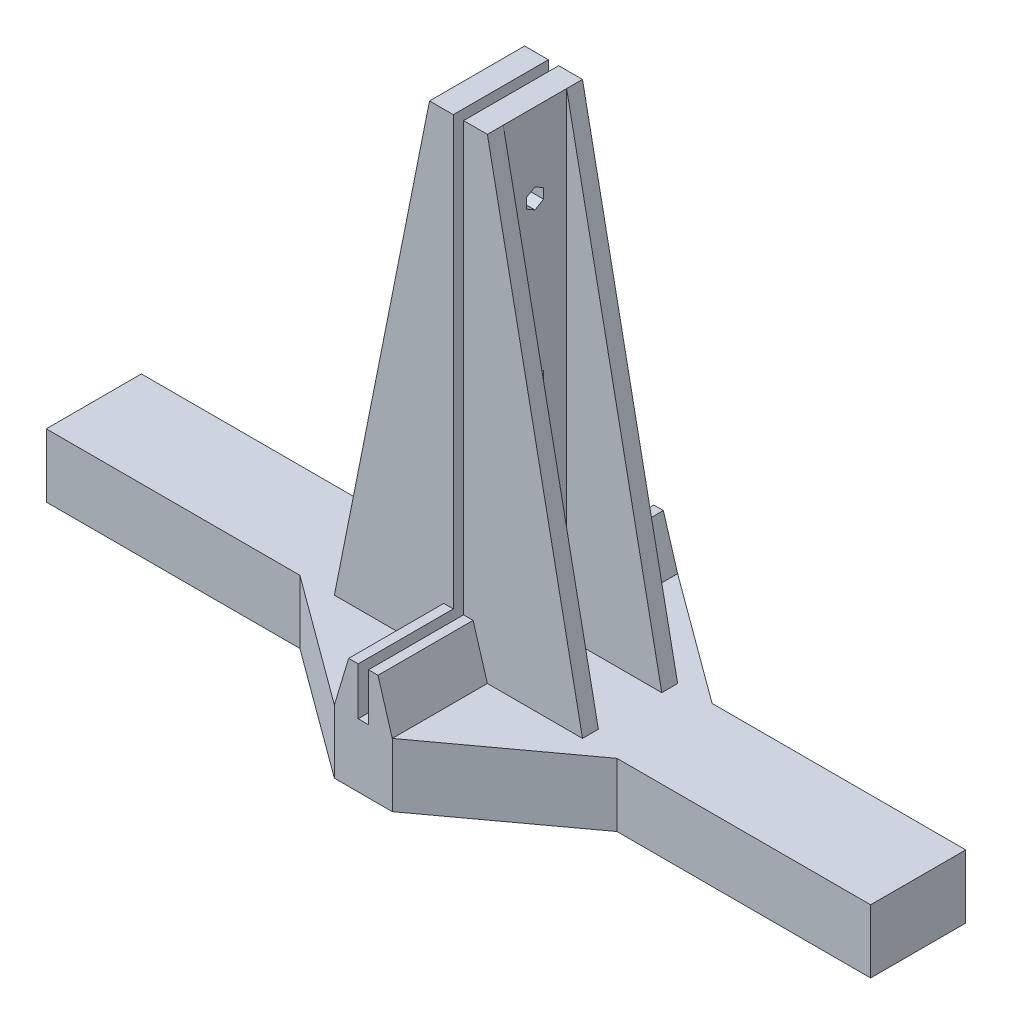
SolidWorks part; units mm, degrees
ref_plane "Front Plane" through (0, 0, 0) normal (0, 0, 1) x (1, 0, 0)
ref_plane "Top Plane" through (0, 0, 0) normal (0, 1, 0) x (1, 0, 0)
ref_plane "Right Plane" through (0, 0, 0) normal (1, 0, 0) x (0, 0, -1)
sketch "Sketch1" plane through (0, 0, 0) normal (0, 0, 1) x (1, 0, 0)
  line L0 (0, 0) -> (130, 0)
  line L1 (55, 0) -> (-55, 0) construction
  line L2 (130, 0) -> (130, 20)
  line L3 (130, 20) -> (9.125, 20)
  line L4 (9.125, 20) -> (9.125, 170)
  line L5 (9.125, 170) -> (1.625, 170)
  line L6 (1.625, 170) -> (1.625, 20)
  line L7 (1.625, 20) -> (-1.625, 20)
  line L8 (-1.625, 20) -> (-1.625, 170)
  line L9 (-1.625, 170) -> (-9.125, 170)
  line L10 (-9.125, 170) -> (-9.125, 20)
  line L11 (-9.125, 20) -> (-130, 20)
  line L12 (-130, 20) -> (-130, 0)
  line L13 (-130, 0) -> (0, 0)
  point P15 (0, 20)
  dimension "D1" = 130
  dimension "D2" = 20
  dimension "D4" = 150
  dimension "D5" = 7.5
  dimension "D6" = 3.25
  dimension "D7" = 260
  dimension "D8" = 7.5
extrude "Boss-Extrude3" add sketch "Sketch1" along normal blind 30
sketch "Sketch3" plane through (9.125, 0, 0) normal (1, 0, 0) x (0, 0, -1)
  line L0 (-30, 170) -> (0, 170) construction
  line L3 (-30, 20) -> (0, 20) construction
  circle A0 centre (-15, 95) radius 1.8
  circle A1 centre (-15, 45) radius 1.8
  circle A2 centre (-15, 145) radius 1.8
  point P0 (-15, 170)
  dimension "D3" = 3.6
  dimension "D2" = 3.6
  dimension "D4" = 25
  dimension "D5" = 50
  dimension "D1" = 50
extrude "Cut-Extrude1" cut sketch "Sketch3" against normal blind 161 and the other way blind 88
sketch "Sketch4" plane through (0, 0, 0) normal (0, 0, 1) x (1, 0, 0)
  line L0 (9.125, 170) -> (39.125, 20)
  line L1 (130, 20) -> (9.125, 20) construction
  line L2 (39.125, 20) -> (9.125, 20)
  line L3 (9.125, 20) -> (9.125, 170)
  line L4 (0, -1000) -> (0, 49000) construction
  line L6 (-9.125, 20) -> (-9.125, 170)
  line L7 (-39.125, 20) -> (-9.125, 20)
  line L8 (-9.125, 170) -> (-39.125, 20)
  dimension "D1" = 30
extrude "Boss-Extrude4" add sketch "Sketch4" along normal blind 5
extrude "Boss-Extrude5" add sketch "Sketch4<2>" against normal blind 5 from surface starting at face at (0, 66.6667, 30)
sketch "Sketch4<2>" plane through (0, 0, 0) normal (0, 0, 1) x (1, 0, 0) same geometry as "Sketch4"
sketch "Sketch5" plane through (0, 20, 0) normal (0, 1, 0) x (1, 0, 0)
  line L0 (9.125, -25) -> (9.125, -5) construction
  line L1 (-9.125, 30) -> (9.125, 30)
  line L2 (-9.125, 30) -> (-9.125, -60) construction
  line L3 (-9.125, -60) -> (9.125, -60)
  line L4 (9.125, 30) -> (9.125, -60) construction
  line L5 (-9.125, 30) -> (9.125, -60) construction
  line L6 (-9.125, -60) -> (9.125, 30) construction
  line L7 (-9.125, -25) -> (-9.125, -5) construction
  line L8 (39.125, 0) -> (9.125, 0) construction
  line L9 (-39.125, 0) -> (-9.125, 30)
  line L10 (-39.125, 0) -> (-9.125, 0)
  line L12 (39.125, 0) -> (9.125, 30)
  line L13 (-39.125, -30) -> (-9.125, -30)
  line L14 (-39.125, -30) -> (-9.125, -60)
  line L15 (-9.125, 0) -> (-9.125, -30)
  line L16 (9.125, -60) -> (39.125, -30)
  line L17 (39.125, -30) -> (39.125, 0)
  point P0 (0, -15)
  point P5 (9.125, -15)
  point P7 (0, 0)
  dimension "D1" = 30
extrude "Boss-Extrude6" add sketch "Sketch5" against normal up to surface (20 mm away) up to face at (0, 0, 15)
sketch "Sketch7" plane through (0, 0, 30) normal (0, 0, 1) x (1, 0, 0)
  line L0 (0, -1000) -> (0, 49000) construction
  line L1 (9.125, 0) -> (-9.125, 0) construction
  line L2 (-1.625, 35) -> (-1.625, 20)
  line L3 (-1.625, 20) -> (-1.625, 170) construction
  line L4 (-1.625, 20) -> (-9.125, 20)
  line L7 (1.625, 20) -> (9.125, 20)
  line L8 (1.625, 35) -> (1.625, 20)
  line L9 (-1.625, 35) -> (-4.625, 35)
  line L10 (-4.625, 35) -> (-9.125, 20)
  line L11 (4.625, 35) -> (9.125, 20)
  line L12 (1.625, 35) -> (4.625, 35)
  point P5 (0, 0)
  dimension "D1" = 15
  dimension "D2" = 3
extrude "Boss-Extrude7" add sketch "Sketch7" along normal up to surface (30 mm away) up to face at (0, 10, 60)
extrude "Boss-Extrude8" add sketch "Sketch7<2>" along direction (0, 0, -1) on the side against the normal up to surface (60 mm away) from surface up to face at (0, 10, -30) starting at face at (-12.875, 95, 0)
sketch "Sketch7<2>" plane through (0, 0, 30) normal (0, 0, 1) x (1, 0, 0) same geometry as "Sketch7"
sketch "Sketch8" plane through (9.125, 0, 0) normal (1, 0, 0) x (0, 0, -1)
  line L1 (-15, 91.8534) -> (-12.275, 93.4267)
  line L2 (-12.275, 93.4267) -> (-12.275, 96.5733)
  line L3 (-12.275, 96.5733) -> (-15, 98.1466)
  line L4 (-15, 98.1466) -> (-17.725, 96.5733)
  line L5 (-17.725, 96.5733) -> (-17.725, 93.4267)
  line L6 (-17.725, 93.4267) -> (-15, 91.8534)
  line L7 (-15, 41.8534) -> (-12.275, 43.4267)
  line L8 (-12.275, 43.4267) -> (-12.275, 46.5733)
  line L9 (-12.275, 46.5733) -> (-15, 48.1466)
  line L10 (-15, 48.1466) -> (-17.725, 46.5733)
  line L11 (-17.725, 46.5733) -> (-17.725, 43.4267)
  line L12 (-17.725, 43.4267) -> (-15, 41.8534)
  line L13 (-15, 141.8534) -> (-12.275, 143.4267)
  line L14 (-12.275, 143.4267) -> (-12.275, 146.5733)
  line L15 (-12.275, 146.5733) -> (-15, 148.1466)
  line L16 (-15, 148.1466) -> (-17.725, 146.5733)
  line L17 (-17.725, 146.5733) -> (-17.725, 143.4267)
  line L18 (-17.725, 143.4267) -> (-15, 141.8534)
  circle A0 centre (-15, 95) radius 2.725 construction
  circle A1 centre (-15, 45) radius 2.725 construction
  circle A2 centre (-15, 145) radius 2.725 construction
  dimension "D1" = 5.45
extrude "Cut-Extrude2" cut sketch "Sketch8" against normal blind 4
sketch "Sketch9" plane through (0, 0, 0) normal (0, -1, 0) x (1, 0, 0)
  line L0 (0, -1000) -> (0, 49000) construction
  line L1 (-9.125, 60) -> (-50, 30)
  line L2 (-130, 30) -> (-39.125, 30) construction
  line L3 (-50, 30) -> (-2, 30)
  line L5 (-1045.1352, 15) -> (48954.8648, 15) construction
  line L6 (-9.125, 60) -> (-2, 60)
  line L7 (-2, 60) -> (-2, 30)
  line L8 (9.125, 60) -> (-9.125, 60) construction
  line L9 (2, 60) -> (2, 30)
  line L10 (9.125, 60) -> (2, 60)
  line L11 (50, 30) -> (2, 30)
  line L12 (9.125, 60) -> (50, 30)
  line L13 (9.125, -30) -> (50, 0)
  line L14 (50, 0) -> (2, 0)
  line L15 (9.125, -30) -> (2, -30)
  line L16 (2, -30) -> (2, 0)
  line L17 (-2, -30) -> (-2, 0)
  line L18 (-9.125, -30) -> (-2, -30)
  line L19 (-50, 0) -> (-2, 0)
  line L20 (-9.125, -30) -> (-50, 0)
  dimension "D1" = 50
  dimension "D2" = 15
  dimension "D3" = 2
extrude "Boss-Extrude10" add sketch "Sketch9" against normal up to surface (20 mm away) up to face at (-54.3437, 20, 15)
